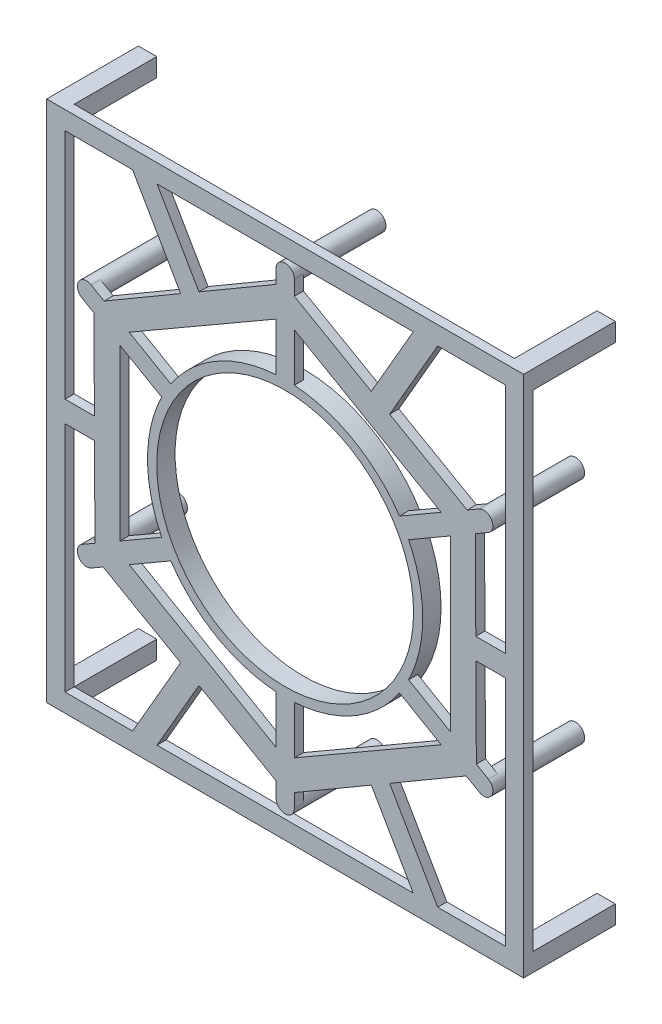
SolidWorks part; units mm, degrees
note: The reader was unsure of these and kept them because the rebuilt part matched: shared geometry of "Sketch1<3>", "Sketch1<5>", "Sketch1<7>", "Sketch1<8>", "Sketch1<9>", "Sketch1<10>", "Sketch1<11>".
ref_plane "Front Plane" through (0, 0, 0) normal (0, 0, 1) x (1, 0, 0)
ref_plane "Top Plane" through (0, 0, 0) normal (0, 1, 0) x (1, 0, 0)
ref_plane "Right Plane" through (0, 0, 0) normal (1, 0, 0) x (0, 0, -1)
sketch "Sketch1" plane through (0, 0, 0) normal (0, 0, 1) x (1, 0, 0)
  line L0 (-70.3283, 36.9379) -> (67.1533, -42.4371)
  line L1 (3.175, -79.375) -> (-3.175, -79.375)
  line L2 (3.175, -79.375) -> (3.175, 79.375)
  line L3 (3.175, 79.375) -> (-3.175, 79.375)
  line L4 (-3.175, -79.375) -> (-3.175, 79.375)
  line L5 (3.175, -1.8331) -> (-3.175, 1.8331)
  line L7 (-70.3283, 36.9379) -> (-67.1533, 42.4371)
  line L8 (-67.1533, 42.4371) -> (70.3283, -36.9379)
  line L9 (67.1533, -42.4371) -> (70.3283, -36.9379)
  line L10 (67.1533, 42.4371) -> (-70.3283, -36.9379)
  line L11 (67.1533, 42.4371) -> (70.3283, 36.9379)
  line L12 (70.3283, 36.9379) -> (-67.1533, -42.4371)
  line L13 (-70.3283, -36.9379) -> (-67.1533, -42.4371)
  line L19 (66.1983, -37.7858) -> (65.8226, 38.4365)
  line L20 (65.8226, 38.4365) -> (-0.3756, 76.2223)
  line L21 (-0.3756, 76.2223) -> (-66.1983, 37.7858)
  line L22 (-66.1983, 37.7858) -> (-65.8226, -38.4365)
  line L23 (-65.8226, -38.4365) -> (0.3756, -76.2223)
  line L24 (0.3756, -76.2223) -> (66.1983, -37.7858)
  line L25 (0, -66.0112) -> (57.1674, -33.0056)
  line L26 (57.1674, -33.0056) -> (57.1674, 33.0056)
  line L27 (57.1674, 33.0056) -> (0, 66.0112)
  line L28 (0, 66.0112) -> (-57.1674, 33.0056)
  line L29 (-57.1674, 33.0056) -> (-57.1674, -33.0056)
  line L30 (-57.1674, -33.0056) -> (0, -66.0112)
  line L31 (-82.55, 90.4875) -> (82.55, 90.4875)
  line L32 (-82.55, 90.4875) -> (-82.55, -90.4875)
  line L33 (-82.55, -90.4875) -> (82.55, -90.4875)
  line L34 (82.55, 90.4875) -> (82.55, -90.4875)
  line L35 (-82.55, 90.4875) -> (82.55, -90.4875) construction
  line L36 (-82.55, -90.4875) -> (82.55, 90.4875) construction
  line L37 (-76.2, 84.1375) -> (76.2, 84.1375)
  line L38 (-76.2, 84.1375) -> (-76.2, -84.1375)
  line L39 (-76.2, -84.1375) -> (76.2, -84.1375)
  line L40 (76.2, 84.1375) -> (76.2, -84.1375)
  line L41 (-76.2, 84.1375) -> (76.2, -84.1375) construction
  line L42 (-76.2, -84.1375) -> (76.2, 84.1375) construction
  line L43 (3.175, -1.8331) -> (-46.5868, -88.023)
  line L44 (-3.175, 1.8331) -> (-52.9368, -84.3568)
  line L45 (-46.5868, -88.023) -> (-52.9368, -84.3568)
  line L46 (0, -3.6662) -> (0, 3.6662)
  line L47 (0, -3.6662) -> (-99.5235, -3.6662)
  line L48 (-99.5235, -3.6662) -> (-99.5235, 3.6662)
  line L49 (0, 3.6662) -> (-99.5235, 3.6662)
  line L50 (-3.175, -1.8331) -> (3.175, 1.8331)
  line L51 (-3.175, -1.8331) -> (-52.9368, 84.3568)
  line L52 (-52.9368, 84.3568) -> (-46.5868, 88.023)
  line L53 (3.175, 1.8331) -> (-46.5868, 88.023)
  line L54 (-3.175, 1.8331) -> (3.175, -1.8331)
  line L55 (-3.175, 1.8331) -> (46.5868, 88.023)
  line L56 (46.5868, 88.023) -> (52.9368, 84.3568)
  line L57 (3.175, -1.8331) -> (52.9368, 84.3568)
  line L58 (0, 3.6662) -> (0, -3.6662)
  line L59 (0, 3.6662) -> (99.5235, 3.6662)
  line L60 (99.5235, 3.6662) -> (99.5235, -3.6662)
  line L61 (0, -3.6662) -> (99.5235, -3.6662)
  line L62 (3.175, 1.8331) -> (-3.175, -1.8331)
  line L63 (3.175, 1.8331) -> (52.9368, -84.3568)
  line L64 (52.9368, -84.3568) -> (46.5868, -88.023)
  line L65 (-3.175, -1.8331) -> (46.5868, -88.023)
  line L67 (-76.2, -84.1375) -> (-82.55, -84.1375)
  line L68 (-76.2, -84.1375) -> (-76.2, -90.4875)
  line L69 (-76.2, -90.4875) -> (-82.55, -90.4875)
  line L70 (-82.55, -84.1375) -> (-82.55, -90.4875)
  line L71 (76.2, -84.1375) -> (82.55, -84.1375)
  line L72 (76.2, -84.1375) -> (76.2, -90.4875)
  line L73 (76.2, -90.4875) -> (82.55, -90.4875)
  line L74 (82.55, -84.1375) -> (82.55, -90.4875)
  line L75 (82.55, 90.4875) -> (76.2, 90.4875)
  line L76 (82.55, 90.4875) -> (82.55, 84.1375)
  line L77 (82.55, 84.1375) -> (76.2, 84.1375)
  line L78 (76.2, 90.4875) -> (76.2, 84.1375)
  line L79 (-82.55, 90.4875) -> (-76.2, 90.4875)
  line L80 (-82.55, 90.4875) -> (-82.55, 84.1375)
  line L81 (-82.55, 84.1375) -> (-76.2, 84.1375)
  line L82 (-76.2, 90.4875) -> (-76.2, 84.1375)
  line L83 (82.55, -84.1375) -> (76.2, -84.1375)
  line L84 (82.55, -84.1375) -> (82.55, -3.6662)
  line L85 (82.55, -3.6662) -> (76.2, -3.6662)
  line L86 (76.2, -84.1375) -> (76.2, -3.6662)
  line L87 (82.55, 3.6662) -> (76.2, 3.6662)
  line L88 (82.55, 3.6662) -> (82.55, 84.1375)
  line L89 (82.55, 84.1375) -> (76.2, 84.1375)
  line L90 (76.2, 3.6662) -> (76.2, 84.1375)
  line L91 (-76.2, -3.6662) -> (-82.55, -3.6662)
  line L92 (-76.2, -3.6662) -> (-76.2, -84.1375)
  line L93 (-76.2, -84.1375) -> (-82.55, -84.1375)
  line L94 (-82.55, -3.6662) -> (-82.55, -84.1375)
  line L95 (-82.55, 84.1375) -> (-76.2, 84.1375)
  line L96 (-82.55, 84.1375) -> (-82.55, 3.6662)
  line L97 (-82.55, 3.6662) -> (-76.2, 3.6662)
  line L98 (-76.2, 84.1375) -> (-76.2, 3.6662)
  circle A0 centre (0, 0) radius 47.625
  circle A1 centre (0, 0) radius 44.45
  circle A2 centre (0, -79.375) radius 3.175
  circle A3 centre (0, 79.375) radius 3.175
  circle A4 centre (-68.7408, 39.6875) radius 3.175
  circle A5 centre (68.7408, -39.6875) radius 3.175
  circle A6 centre (68.7408, 39.6875) radius 3.175
  circle A7 centre (-68.7408, -39.6875) radius 3.175
  circle A8 centre (0, 0) radius 57.1674 construction
  circle A9 centre (0, 0) radius 66.0112 construction
  point P30 (0, 0)
  point P77 (0, 0)
  dimension "D1" = 95.25
  dimension "D2" = 3.175
  dimension "D3" = 158.75
  dimension "D4" = 6.35
  dimension "D5" = 3
  dimension "D6" = 165.1
  dimension "D7" = 180.975
  dimension "D8" = 6.35
  dimension "D9" = 6.35
  dimension "D10" = 60
  dimension "D11" = 60
  dimension "D12" = 60
  dimension "D13" = 60
  dimension "D14" = 60
  dimension "D15" = 60
  dimension "D16" = 6
extrude "Boss-Extrude1" add sketch "Sketch1" along normal blind 3.175 contours L29 L47 L22 L10 | L44 L30 L12 L23 | L30 L29 L10 L22 L23 L12 | L29 L49 L22 L47 | L49 L29 L0 L22 | L29 L28 L8 L21 L22 L0 | L28 L51 L21 L8 | L28 L53 L21 L51 | L53 L28 L4 L21 | L28 L27 L2 L20 L21 L4 | L27 L55 L20 L2 | L27 L57 L20 L55 | L57 L27 L10 L20 | L26 L59 L19 L12 | L27 L26 L12 L19 L20 L10 | L26 L61 L19 L59 | L61 L26 L8 L19 | L26 L25 L0 L24 L19 L8 | L25 L63 L24 L0 | L25 L65 L24 L63 | L65 L25 L2 L24 | L30 L4 L23 L24 L2 L25 | L30 L43 L23 L4 | L30 L44 L23 L43
extrude "Boss-Extrude2" add sketch "Sketch1<3>" along normal blind 3.175 contours A0 L4 L30 L25 L2 | L25 L2 L24 L0 | L30 L4 L23 L24 L2 L25 | L30 L12 L23 L4 | L29 L0 L22 L10 | L30 L29 L10 L22 L23 L12 | L29 L28 L8 L21 L22 L0 | A0 L8 L28 L29 L0 | L28 L4 L21 L8 | L28 L27 L2 L20 L21 L4 | A0 L2 L27 L28 L4 | L27 L10 L20 L2 | L27 L26 L12 L19 L20 L10 | A0 L12 L26 L27 L10 | L26 L8 L19 L12 | L26 L25 L0 L24 L19 L8 | A0 L0 L25 L26 L8 | A0 L10 L29 L30 L12
sketch "Sketch1<3>" plane through (0, 0, 0) normal (0, 0, 1) x (1, 0, 0) same geometry as "Sketch1"
extrude "Boss-Extrude3" add sketch "Sketch1<5>" along normal blind 3.175 contours A7 L12 L23 | A7 L22 L10 | A2 L23 L4 | A2 L2 L24 | A4 L0 L22 | A4 L21 L8 | A3 L4 L21 | A3 L20 L2 | A6 L19 L12 | A6 L10 L20 | A5 L24 L0 | A5 L8 L19
sketch "Sketch1<5>" plane through (0, 0, 0) normal (0, 0, 1) x (1, 0, 0) same geometry as "Sketch1"
extrude "Boss-Extrude4" add sketch "Sketch1<7>" along normal blind 3.175 and the other way blind 28.575 contours A2 | A5 | A6 | A3 | A4 | A7
sketch "Sketch1<7>" plane through (0, 0, 0) normal (0, 0, 1) x (1, 0, 0) same geometry as "Sketch1"
extrude "Boss-Extrude5" add sketch "Sketch1<8>" along normal blind 3.175 and the other way blind 3.175 contours A1 L57 A0 L55 | A1 L10 A0 L57 | A1 L12 A0 L10 | A1 L59 A0 L12 | A1 L61 A0 L59 | A1 L8 A0 L61 | A1 L0 A0 L8 | A1 L63 A0 L0 | A1 L65 A0 L63 | A1 L2 A0 L65 | A1 L4 A0 L2 | A1 L43 A0 L4 | A1 L44 A0 L43 | A1 L12 A0 L44 | A1 L10 A0 L12 | A1 L47 A0 L10 | A1 L49 A0 L47 | A1 L0 A0 L49 | A1 L8 A0 L0 | A1 L51 A0 L8 | A1 L53 A0 L51 | A1 L4 A0 L53 | A1 L2 A0 L4 | A1 L55 A0 L2
sketch "Sketch1<8>" plane through (0, 0, 0) normal (0, 0, 1) x (1, 0, 0) same geometry as "Sketch1"
extrude "Boss-Extrude6" add sketch "Sketch1<9>" along normal blind 3.175 contours L40 L59 L34 L31 L32 L49 L38 L37 L51 L52 L53 L55 L56 L57 | L20 L57 L37 L55 | L37 L57 L56 L55 | L37 L53 L52 L51 | L38 L49 L32 L47 | L65 L39 L43 L45 L44 L38 L47 L32 L33 L34 L61 L40 L63 L64 | L45 L43 L39 L44 | L39 L65 L64 L63 | L40 L61 L34 L59 | L21 L53 L37 L51 | L22 L49 L38 L47 | L23 L44 L39 L43 | L24 L65 L39 L63 | L19 L61 L40 L59
sketch "Sketch1<9>" plane through (0, 0, 0) normal (0, 0, 1) x (1, 0, 0) same geometry as "Sketch1"
extrude "Boss-Extrude7" add sketch "Sketch1<10>" along normal blind 3.175 and the other way blind 28.575 contours L71 L72 L33 L34 | L68 L67 L32 L33 | L82 L31 L32 L81 | L31 L78 L77 L34
sketch "Sketch1<10>" plane through (0, 0, 0) normal (0, 0, 1) x (1, 0, 0) same geometry as "Sketch1"
extrude "Boss-Extrude8" add sketch "Sketch1<11>" along normal blind 3.175 contours L67 L38 L47 L32 | L81 L32 L49 L38 | L34 L77 L40 L59 | L40 L71 L34 L61
sketch "Sketch1<11>" plane through (0, 0, 0) normal (0, 0, 1) x (1, 0, 0) same geometry as "Sketch1"
